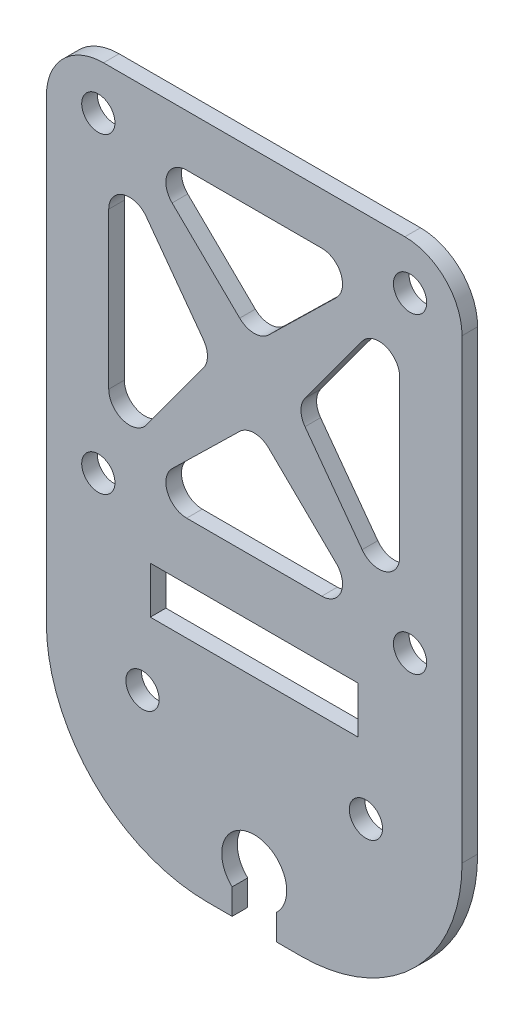
SolidWorks part; units mm, degrees
ref_plane "Front Plane" through (0, 0, 0) normal (0, 0, 1) x (1, 0, 0)
ref_plane "Top Plane" through (0, 0, 0) normal (0, 1, 0) x (1, 0, 0)
ref_plane "Right Plane" through (0, 0, 0) normal (1, 0, 0) x (0, 0, -1)
sketch "Sketch1" plane through (0, 0, 0) normal (0, 0, 1) x (1, 0, 0)
  line L0 (-20, 13.95) -> (-20, -30)
  line L1 (-4.5, -45.5) -> (-2.124, -45.5)
  line L2 (20, -30) -> (20, 13.95)
  line L3 (14.5, 19.45) -> (-14.5, 19.45)
  line L4 (0, 31.9916) -> (0, -70.8358) construction
  line L5 (-10, -20) -> (10, -20)
  line L6 (-10, -20) -> (-10, -24.5)
  line L7 (-10, -24.5) -> (10, -24.5)
  line L8 (10, -20) -> (10, -24.5)
  line L9 (-53.3333, 0) -> (49.6454, 0) construction
  line L10 (-2.124, -43.0423) -> (-2.124, -45.5)
  line L11 (2.124, -43.0423) -> (2.124, -45.5)
  line L12 (2.124, -45.5) -> (4.5, -45.5)
  line L13 (-14, 7.5) -> (-14, -7.5)
  line L14 (-10.3872, -8.6827) -> (-4.8872, -1.1827)
  line L15 (-4.8872, 1.1827) -> (-10.3872, 8.6827)
  line L16 (4.8872, 1.1827) -> (10.3872, 8.6827)
  line L17 (10.3872, -8.6827) -> (4.8872, -1.1827)
  line L18 (14, 7.5) -> (14, -7.5)
  line L19 (-7.8976, 11.0694) -> (-1.3976, 4.7194)
  line L20 (1.3976, 4.7194) -> (7.8976, 11.0694)
  line L21 (6.5, 14.5) -> (-6.5, 14.5)
  line L22 (6.5, -14.5) -> (-6.5, -14.5)
  line L23 (1.3976, -4.7194) -> (7.8976, -11.0694)
  line L24 (-7.8976, -11.0694) -> (-1.3976, -4.7194)
  circle A0 centre (-15, 15) radius 1.6
  circle A1 centre (15, 15) radius 1.6
  circle A2 centre (15, -15) radius 1.6
  circle A3 centre (-15, -15) radius 1.6
  arc A4 (14.5, 19.45) -> (20, 13.95) centre (14.5, 13.95) cw
  arc A5 (-14.5, 19.45) -> (-20, 13.95) centre (-14.5, 13.95) ccw
  arc A6 (20, -30) -> (4.5, -45.5) centre (4.5, -30) cw
  arc A7 (-4.5, -45.5) -> (-20, -30) centre (-4.5, -30) cw
  arc A8 (2.124, -43.0423) -> (-2.124, -43.0423) centre (0, -40.75) ccw
  circle A9 centre (10.75, -30.95) radius 1.6
  circle A10 centre (-10.75, -30.95) radius 1.6
  arc A11 (-10.3872, 8.6827) -> (-14, 7.5) centre (-12, 7.5) ccw
  arc A12 (-14, -7.5) -> (-10.3872, -8.6827) centre (-12, -7.5) ccw
  arc A13 (-4.8872, -1.1827) -> (-4.8872, 1.1827) centre (-6.5, 0) ccw
  arc A14 (4.8872, -1.1827) -> (4.8872, 1.1827) centre (6.5, 0) cw
  arc A15 (14, -7.5) -> (10.3872, -8.6827) centre (12, -7.5) cw
  arc A16 (10.3872, 8.6827) -> (14, 7.5) centre (12, 7.5) cw
  arc A17 (-1.3976, 4.7194) -> (1.3976, 4.7194) centre (0, 6.15) ccw
  arc A18 (-6.5, 14.5) -> (-7.8976, 11.0694) centre (-6.5, 12.5) ccw
  arc A19 (7.8976, 11.0694) -> (6.5, 14.5) centre (6.5, 12.5) ccw
  arc A20 (7.8976, -11.0694) -> (6.5, -14.5) centre (6.5, -12.5) cw
  arc A21 (-6.5, -14.5) -> (-7.8976, -11.0694) centre (-6.5, -12.5) cw
  arc A22 (-1.3976, -4.7194) -> (1.3976, -4.7194) centre (0, -6.15) cw
  dimension "D4" = 3.2
  dimension "D14" = 5.5
  dimension "D15" = 20
  dimension "D22" = 3.2
  dimension "D17" = 15.5
  dimension "D18" = 6.25
  dimension "D25" = 4
  dimension "D31" = 4
  dimension "D2" = 40.75
  dimension "D3" = 45.5
  dimension "D5" = 15
  dimension "D6" = 15
  dimension "D7" = 4.45
  dimension "D8" = 30
  dimension "D9" = 30
  dimension "D10" = 20
  dimension "D11" = 4.5
  dimension "D12" = 20
  dimension "D13" = 20
  dimension "D16" = 10
  dimension "D19" = 2.124
  dimension "D20" = 2.124
  dimension "D21" = 30.95
  dimension "D23" = 10.75
  dimension "D24" = 10.75
  dimension "D26" = 6.5
  dimension "D27" = 7.5
  dimension "D28" = 12
  dimension "D29" = 7.5
  dimension "D30" = 12
  dimension "D32" = 12.5
  dimension "D33" = 6.15
  dimension "D34" = 6.5
  dimension "D35" = 6.5
extrude "Boss-Extrude1" add sketch "Sketch1" along normal mid plane 1.5
